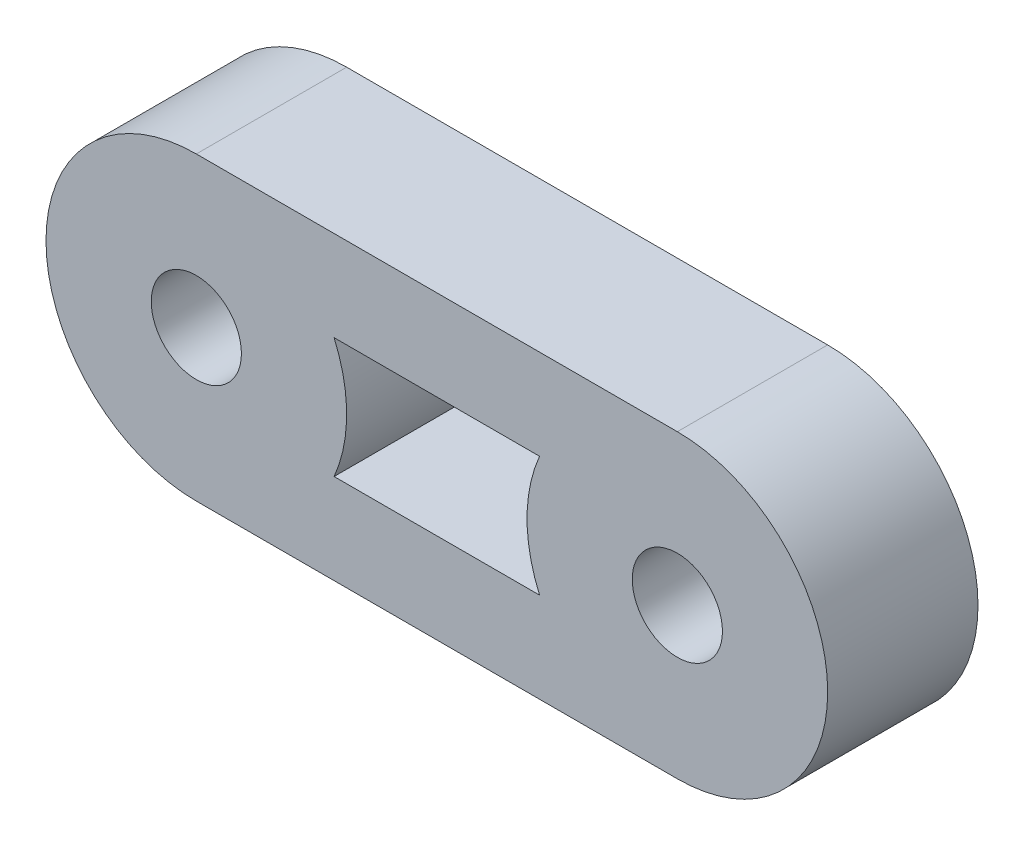
SolidWorks part; units mm, degrees
material "1060 Alloy"
ref_plane "Front Plane" through (0, 0, 0) normal (0, 0, 1) x (1, 0, 0)
ref_plane "Top Plane" through (0, 0, 0) normal (0, 1, 0) x (1, 0, 0)
ref_plane "Right Plane" through (0, 0, 0) normal (1, 0, 0) x (0, 0, -1)
sketch "Sketch1" plane through (0, 0, 0) normal (0, 0, 1) x (1, 0, 0)
  line L0 (0, 0) -> (16, 0)
  line L1 (0, -5) -> (16, -5)
  line L2 (0, 5) -> (16, 5)
  circle A0 centre (16, 0) radius 1.5
  circle A1 centre (0, 0) radius 1.5
  arc A2 (0, -5) -> (0, 5) centre (0, 0) cw
  arc A3 (16, -5) -> (16, 5) centre (16, 0) ccw
  dimension "D2" = 3
  dimension "D1" = 3
extrude "Extrude1" add sketch "Sketch1" along normal blind 5 contours L1 A3 L2 A2 A1 A0 region at (-4.7214, 0, 0)
sketch "Sketch2" plane through (0, 0, 5) normal (0, 0, 1) x (1, 0, 0)
  line L4 (0, -2) -> (16, -2)
  line L5 (16, 2) -> (0, 2)
  line L6 (4.5826, -2) -> (11.4174, -2)
  line L7 (11.4174, 2) -> (4.5826, 2)
  arc A2 (4.5826, -2) -> (4.5826, 2) centre (0, 0) ccw
  arc A3 (11.4174, 2) -> (11.4174, -2) centre (16, 0) ccw
  arc A4 (16, -2) -> (16, 2) centre (16, 0) ccw
  arc A5 (0, 2) -> (0, -2) centre (0, 0) ccw
  dimension "D1" = 3
extrude "Cut-Extrude1" cut sketch "Sketch2" against normal blind 10
move or copy body "Body-Move/Copy1" [suppressed] bodies to move or copy 103
move or copy body "Body-Move/Copy2" [suppressed] bodies to move or copy 103
